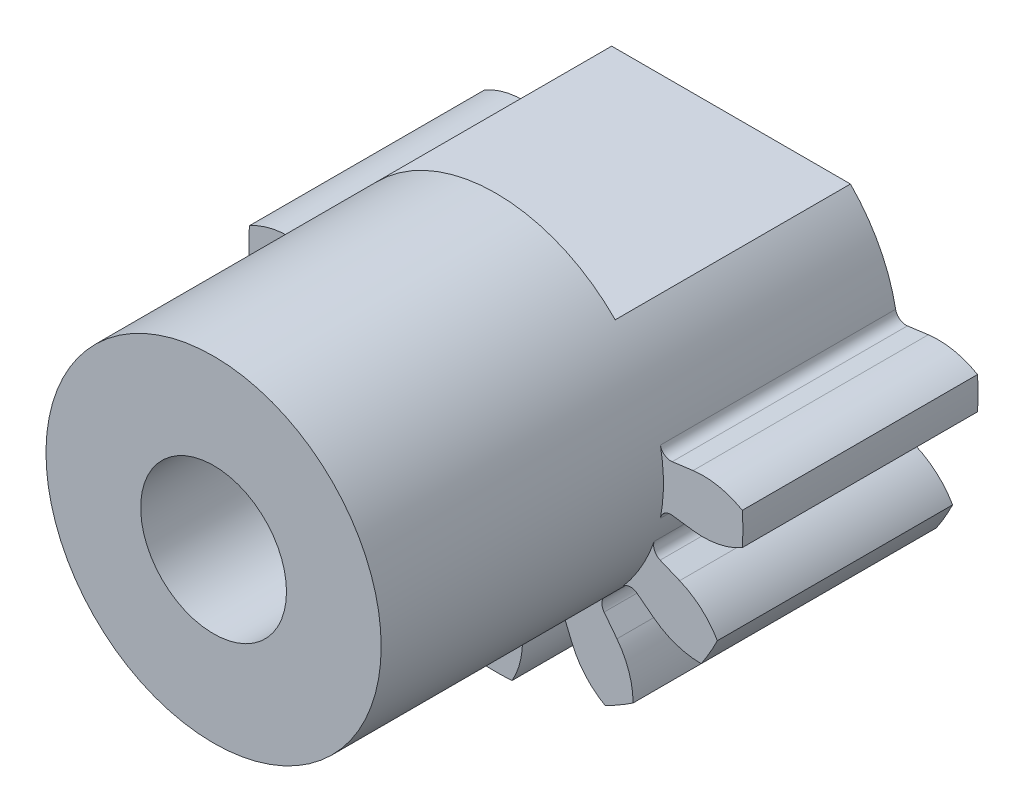
SolidWorks part; units mm, degrees
ref_plane "Front Plane" through (0, 0, 0) normal (0, 0, 1) x (1, 0, 0)
ref_plane "Top Plane" through (0, 0, 0) normal (0, 1, 0) x (1, 0, 0)
ref_plane "Right Plane" through (0, 0, 0) normal (1, 0, 0) x (0, 0, -1)
sketch "Esquisse1" plane through (0, 0, 0) normal (0, 0, 1) x (1, 0, 0)
  line L0 (0, 0) -> (22.1157, 0) construction
  line L1 (0, 0) -> (24.1492, 6.4708) construction
  line L2 (0, 0) -> (24.1492, -6.4708) construction
  line L3 (0, 0) -> (24.9429, 3.2838) construction
  line L4 (0, 0) -> (6.8822, 1.8441)
  line L5 (0, 0) -> (19.7164, -2.5957) construction
  line L6 (0, 0) -> (6.8822, -1.8441)
  line L7 (0, 0) -> (17.7915, 1.1661) construction
  line L8 (7.064, 0.93) -> (8.3849, 1.1039)
  line L9 (7.064, -0.93) -> (8.3849, -1.1039)
  line L10 (0, 0) -> (17.695, -1.1598) construction
  circle A0 centre (0, 0) radius 9 construction
  circle A1 centre (0, 0) radius 10.5 construction
  circle A2 centre (0, 0) radius 7.125 construction
  circle A3 centre (0, 0) radius 8.4572 construction
  arc A4 (6.8822, 1.8441) -> (7.064, 0.93) centre (0, 0) cw
  arc A5 (6.8822, -1.8441) -> (7.064, -0.93) centre (0, 0) ccw
  arc A6 (8.3849, 1.1039) -> (10.4775, 0.6867) centre (8.8176, -2.1828) cw
  arc A7 (10.4775, 0.6867) -> (10.4775, -0.6867) centre (0, 0) cw
  arc A8 (8.3849, -1.1039) -> (10.4775, -0.6867) centre (8.8176, 2.1828) ccw
  dimension "PrimitiveDiameter" = 18
  dimension "OutsideDiameter" = 21
  dimension "InternalDiameter" = 14.25
  dimension "BaseDiameter" = 16.9145
  dimension "DemiToothAngle" = 15
  dimension "QuartToothAngle" = 7.5
  dimension "D1" = 7.5
  dimension "D2" = 3.75
  dimension "D3" = 3.75
extrude "MainGear" add sketch "Esquisse1" along normal blind 10
fillet "Congé1" radius 0.45 2 edges at (7.064, -0.93, 5) (7.064, 0.93, 5)
ref_axis "Axe1" through (0, 0, 10) along (0, 0, -1)
pattern_circular "Répétition circulaire1" count 7 every 30 about axis through (0, 0, 10) along (0, 0, -1) of "MainGear", "Congé1"
sketch "Esquisse3" plane through (0, 0, 0) normal (0, 0, 1) x (1, 0, 0)
  circle A0 centre (0, 0) radius 3.1
  dimension "D1" = 6.2
sketch "Esquisse5" plane through (0, 0, 10) normal (0, 0, 1) x (1, 0, 0)
  circle A0 centre (0, 0) radius 7.125
extrude "MainBaseCircle" add sketch "Esquisse5" against normal through all
sketch "Esquisse7" plane through (0, 0, 10) normal (0, 0, 1) x (1, 0, 0)
  line L0 (-5.076, 5) -> (5.076, 5)
  circle A0 centre (0, 0) radius 7.125 construction
  arc A1 (5.076, 5) -> (-5.076, 5) centre (0, 0) ccw
  dimension "D1" = 5
extrude "RemoveGearTop" cut sketch "Esquisse7" against normal blind 10
sketch "Esquisse9" plane through (0, 0, 10) normal (0, 0, 1) x (1, 0, 0)
  circle A0 centre (0, 0) radius 7.125
  circle A1 centre (0, 0) radius 7.125 construction
  circle A2 centre (0, 0) radius 3.05
  dimension "D1" = 6.1
extrude "GearBottomFix" add sketch "Esquisse9" along normal blind 12
extrude "GearHole" cut sketch "Esquisse3" along normal through all
sketch "Esquisse10" plane through (0, 0, 0) normal (0, 0, -1) x (-1, 0, 0)
  line L0 (-1.833, 2.5) -> (1.833, 2.5)
  circle A0 centre (0, 0) radius 3.1 construction
  arc A1 (-1.833, 2.5) -> (1.833, 2.5) centre (0, 0) cw
  dimension "D1" = 2.5
extrude "MeplatHole" add sketch "Esquisse10" against normal blind 15
equation "\"Modulo\"= 1.5mm"
equation "\"ToothCount\"= 12"
equation "\"PrimitiveDiameter@Esquisse1\"= \"Modulo\" * \"ToothCount\""
equation "\"OutsideDiameter@Esquisse1\" = \"Modulo\" *  ( \"ToothCount\" + 2 ) "
equation "\"InternalDiameter@Esquisse1\" = \"PrimitiveDiameter@Esquisse1\" - \"Modulo\" * 2.5"
equation "\"Angle\"= 20deg"
equation "\"BaseDiameter@Esquisse1\" = \"PrimitiveDiameter@Esquisse1\" * cos ( \"Angle\" ) "
equation "\"DemiToothAngle@Esquisse1\" = 180 / \"ToothCount\""
equation "\"QuartToothAngle@Esquisse1\"= \"DemiToothAngle@Esquisse1\" / 2"
equation "\"D1@Esquisse1\"= \"QuartToothAngle@Esquisse1\""
equation "\"D2@Esquisse1\"= \"QuartToothAngle@Esquisse1\" / 2"
equation "\"D3@Esquisse1\"= \"D2@Esquisse1\""
equation "\"D2@Répétition circulaire1\"=360/\"ToothCount\""
equation "\"D1@Congé1\"=\"Modulo\"*0.3"
